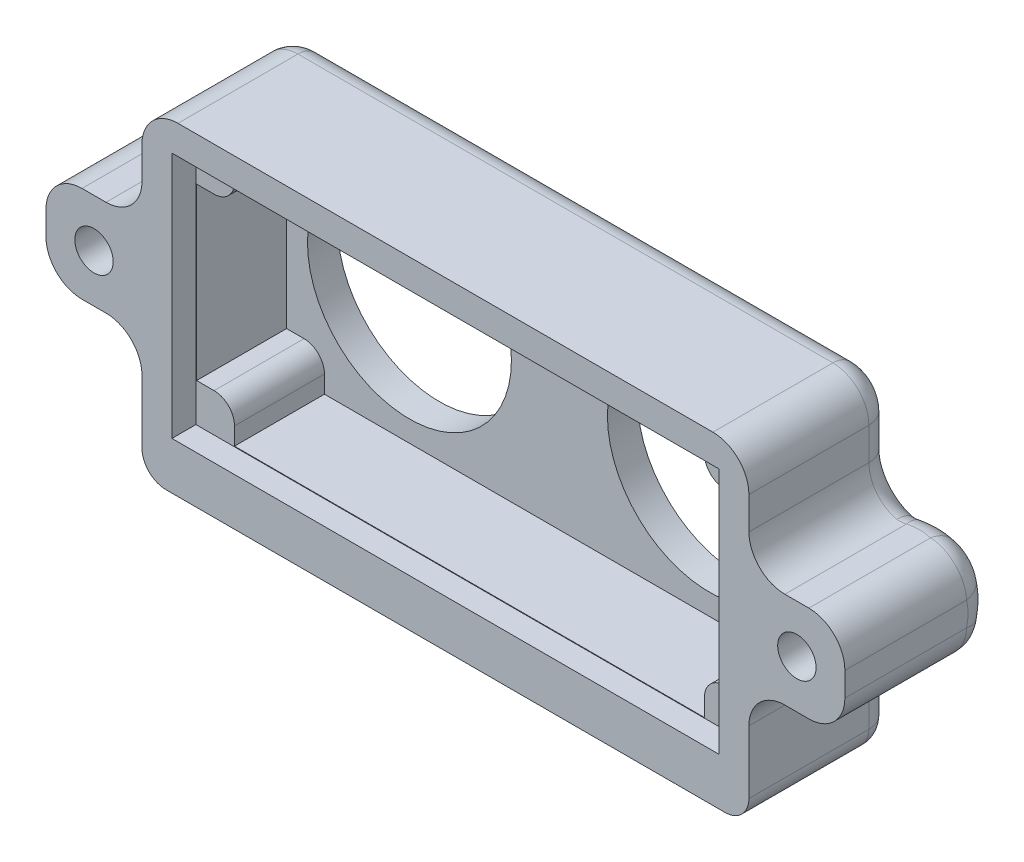
SolidWorks part; units mm, degrees
ref_plane "Plan de face" through (0, 0, 0) normal (0, 0, 1) x (1, 0, 0)
ref_plane "Plan de dessus" through (0, 0, 0) normal (0, 1, 0) x (1, 0, 0)
ref_plane "Plan de droite" through (0, 0, 0) normal (1, 0, 0) x (0, 0, -1)
sketch "Esquisse1" plane through (0, 0, 0) normal (0, 0, 1) x (1, 0, 0)
  line L0 (-21.285, -8.79) -> (21.285, -8.79) construction
  line L1 (-21.285, -8.79) -> (-21.285, 8.79) construction
  line L2 (-21.285, 8.79) -> (21.285, 8.79) construction
  line L3 (21.285, -8.79) -> (21.285, 8.79) construction
  line L4 (-21.285, -8.79) -> (21.285, 8.79) construction
  line L5 (-21.285, 8.79) -> (21.285, -8.79) construction
  line L6 (-22.795, -10.2) -> (22.795, -10.2)
  line L7 (-22.795, -10.2) -> (-22.795, 10.2)
  line L8 (-22.795, 10.2) -> (22.795, 10.2)
  line L9 (22.795, -10.2) -> (22.795, 10.2)
  line L10 (-22.795, -10.2) -> (22.795, 10.2) construction
  line L11 (-22.795, 10.2) -> (22.795, -10.2) construction
  circle A0 centre (-21.285, 8.79) radius 0.825 construction
  circle A1 centre (21.285, 8.79) radius 0.825 construction
  circle A2 centre (21.285, -8.79) radius 0.825 construction
  circle A3 centre (-21.285, -8.79) radius 0.825 construction
  point P0 (0, 0)
  point P5 (0, 0)
  dimension "D5" = 1.65
  dimension "D1" = 42.57
  dimension "D2" = 17.58
  dimension "D3" = 20.4
  dimension "D4" = 45.59
extrude "Boss.-Extru.1" add sketch "Esquisse1" along normal blind 12
sketch "Esquisse3" plane through (0, 0, 12) normal (0, 0, 1) x (1, 0, 0)
  line L0 (22.795, 10.2) -> (-22.795, 10.2) construction
  line L1 (-25.295, 12.7) -> (25.295, 12.7)
  line L2 (-25.295, 12.7) -> (-25.295, -12.7)
  line L3 (-25.295, -12.7) -> (25.295, -12.7)
  line L4 (25.295, 12.7) -> (25.295, -12.7)
  line L5 (-25.295, 12.7) -> (25.295, -12.7) construction
  line L6 (-25.295, -12.7) -> (25.295, 12.7) construction
  line L7 (-22.795, 10.2) -> (-22.795, -10.2) construction
  line L9 (22.795, -10.2) -> (-22.795, -10.2)
  line L10 (22.795, -10.2) -> (22.795, 10.2)
  line L11 (22.795, 10.2) -> (-22.795, 10.2)
  line L12 (-22.795, -10.2) -> (-22.795, 10.2)
  line L13 (22.795, -10.2) -> (-22.795, 10.2) construction
  line L14 (22.795, 10.2) -> (-22.795, -10.2) construction
  point P0 (0, 0)
  point P10 (0, 0)
  dimension "D1" = 2.5
  dimension "D2" = 2.5
extrude "Boss.-Extru.2" add sketch "Esquisse3" against normal blind 12
sketch "Esquisse4" plane through (0, 0, 12) normal (0, 0, 1) x (1, 0, 0)
  line L0 (-19.585, 8.79) -> (-19.585, 10.25)
  line L5 (-23.8, -10.25) -> (23.8, -10.25) construction
  line L6 (-23.8, -10.25) -> (-23.8, 10.25) construction
  line L11 (-23.8, 10.25) -> (23.8, 10.25) construction
  line L12 (23.8, -10.25) -> (23.8, 10.25) construction
  line L13 (-23.8, -10.25) -> (23.8, 10.25) construction
  line L14 (-23.8, 10.25) -> (23.8, -10.25) construction
  line L15 (-23.8, 7.09) -> (-21.285, 7.09)
  line L16 (-21.285, -7.09) -> (-23.8, -7.09)
  line L17 (-19.585, -8.79) -> (-19.585, -10.25)
  line L18 (19.585, -8.79) -> (19.585, -10.25)
  line L19 (21.285, -7.09) -> (23.8, -7.09)
  line L20 (19.585, 8.79) -> (19.585, 10.25)
  line L21 (21.285, 7.09) -> (23.8, 7.09)
  line L22 (-19.585, 10.25) -> (19.585, 10.25)
  line L23 (23.8, 7.09) -> (23.8, -7.09)
  line L24 (-19.585, -10.25) -> (19.585, -10.25)
  line L25 (-23.8, -7.09) -> (-23.8, 7.09)
  arc A4 (-19.585, 8.79) -> (-21.285, 7.09) centre (-21.285, 8.79) cw
  circle A5 centre (-21.285, 8.79) radius 1.7 construction
  circle A6 centre (21.285, 8.79) radius 1.7 construction
  circle A7 centre (21.285, -8.79) radius 1.7 construction
  circle A8 centre (-21.285, -8.79) radius 1.7 construction
  arc A9 (-21.285, -7.09) -> (-19.585, -8.79) centre (-21.285, -8.79) cw
  arc A10 (19.585, -8.79) -> (21.285, -7.09) centre (21.285, -8.79) cw
  arc A11 (21.285, 7.09) -> (19.585, 8.79) centre (21.285, 8.79) cw
  point P5 (0, 0)
  point P10 (0, 0)
  point P22 (0, 0)
  point P27 (0, 0)
  point P32 (0, 0)
  dimension "D1" = 3.4
  dimension "D2" = 20.5
  dimension "D3" = 47.6
extrude "Enlèv. mat.-Extru.1" cut sketch "Esquisse4" against normal blind 12
sketch "Esquisse5" plane through (0, 0, 0) normal (0, 0, -1) x (-1, 0, 0)
  line L1 (-7.5, -14.25) -> (7.5, -14.25)
  line L2 (-7.5, -14.25) -> (-7.5, -10.25)
  line L3 (-7.5, -10.25) -> (7.5, -10.25)
  line L4 (7.5, -14.25) -> (7.5, -10.25)
  line L5 (-7.5, -14.25) -> (7.5, -10.25) construction
  line L6 (-7.5, -10.25) -> (7.5, -14.25) construction
  line L8 (19.585, -10.25) -> (-19.585, -10.25) construction
  point P0 (0, -12.25)
  dimension "D1" = 15
  dimension "D2" = 4
extrude "Boss.-Extru.5" [suppressed] add sketch "Esquisse5" along normal blind 100
sketch "Esquisse7" plane through (0, 12.7, 0) normal (0, 1, 0) x (1, 0, 0)
  line L0 (25.295, 0) -> (-25.295, 0) construction
  line L1 (-5.25, -4) -> (5.25, -4)
  line L2 (-5.25, -4) -> (-5.25, 0)
  line L3 (-5.25, 0) -> (5.25, 0)
  line L4 (5.25, -4) -> (5.25, 0)
  line L5 (-5.25, -4) -> (5.25, 0) construction
  line L6 (-5.25, 0) -> (5.25, -4) construction
  point P0 (0, -2)
  dimension "D1" = 10.5
  dimension "D2" = 4
extrude "Enlèv. mat.-Extru.2" [suppressed] cut sketch "Esquisse7" against normal blind 5
sketch "Esquisse8" plane through (0, -12.7, 0) normal (0, -1, 0) x (1, 0, 0)
  line L0 (-25.295, 12) -> (25.295, 12) construction
  line L1 (-6.1299, 6) -> (6.1299, 6)
  line L2 (-6.1299, 6) -> (-6.1299, 12)
  line L3 (-6.1299, 12) -> (6.1299, 12)
  line L4 (6.1299, 6) -> (6.1299, 12)
  line L5 (-6.1299, 6) -> (6.1299, 12) construction
  line L6 (-6.1299, 12) -> (6.1299, 6) construction
  point P0 (0, 9)
  dimension "D1" = 6
extrude "Boss.-Extru.6" [suppressed] add sketch "Esquisse8" along normal blind 7
sketch "Esquisse9" [suppressed] plane through (0, 0, 0) normal (0, 0, -1) x (-1, 0, 0)
  line L0 (-6.1299, -19.7) -> (-6.1299, -12.7) construction
  circle A0 centre (0, -16.2) radius 1.6
  point P5 (-6.1299, -16.2)
  dimension "D1" = 3.2
extrude "Enlèv. mat.-Extru.3" [suppressed] cut sketch "Esquisse9" against normal blind 6
sketch "Esquisse10" [suppressed] plane through (0, 0, 0) normal (0, 0, -1) x (-1, 0, 0)
  line L0 (6.1299, -19.7) -> (-6.1299, -19.7) construction
  line L1 (3.2332, -16.2) -> (1.6166, -13.4)
  line L2 (1.6166, -13.4) -> (-1.6166, -13.4)
  line L3 (-1.6166, -13.4) -> (-3.2332, -16.2)
  line L4 (-3.2332, -16.2) -> (-1.6166, -19)
  line L5 (-1.6166, -19) -> (1.6166, -19)
  line L6 (1.6166, -19) -> (3.2332, -16.2)
  circle A0 centre (0, -16.2) radius 2.8 construction
  dimension "D1" = 5.6
extrude "Enlèv. mat.-Extru.4" [suppressed] cut sketch "Esquisse10" against normal blind 2.5
fillet "Congé1" [suppressed] radius 3
fillet "Congé2" radius 3 2 edges at (25.295, 12.7, 6) (-25.295, 12.7, 6)
sketch "Esquisse11" [suppressed] plane through (0, 0, -100) normal (0, 0, -1) x (-1, 0, 0)
  line L1 (-15, -14.25) -> (15, -14.25)
  line L2 (-15, -14.25) -> (-15, 19.75)
  line L3 (-15, 19.75) -> (15, 19.75)
  line L4 (15, -14.25) -> (15, 19.75)
  line L5 (7.5, -10.25) -> (-7.5, -10.25) construction
  line L6 (-10, 14.75) -> (10, 14.75) construction
  line L7 (-10, 14.75) -> (-10, -5.25) construction
  line L8 (-10, -5.25) -> (10, -5.25) construction
  line L9 (10, 14.75) -> (10, -5.25) construction
  line L10 (-7.5, -14.25) -> (7.5, -14.25) construction
  circle A0 centre (-10, 14.75) radius 1.1581
  circle A1 centre (10, 14.75) radius 1.184
  circle A2 centre (10, -5.25) radius 1.2948
  circle A3 centre (-10, -5.25) radius 1.2189
  point P6 (0, 19.75)
  point P12 (0, -5.25)
  dimension "D1" = 5
  dimension "D2" = 20
  dimension "D3" = 20
  dimension "D4" = 5
  dimension "D5" = 5
extrude "Boss.-Extru.7" [suppressed] add sketch "Esquisse11" against normal blind 7.5
fillet "Congé3" [suppressed] radius 3
sketch "Esquisse12" [suppressed] plane through (0, 0, -92.5) normal (0, 0, 1) x (1, 0, 0)
  line L0 (-10, 14.75) -> (10, -5.25) construction
  line L1 (-12.2862, 17.0362) -> (-13.123, 13.9132)
  line L2 (-13.123, 13.9132) -> (-10.8368, 11.627)
  line L3 (-10.8368, 11.627) -> (-7.7138, 12.4638)
  line L4 (-7.7138, 12.4638) -> (-6.877, 15.5868)
  line L5 (-6.877, 15.5868) -> (-9.1632, 17.873)
  line L6 (-9.1632, 17.873) -> (-12.2862, 17.0362)
  line L7 (12.2862, 17.0362) -> (9.1632, 17.873)
  line L8 (9.1632, 17.873) -> (6.877, 15.5868)
  line L9 (6.877, 15.5868) -> (7.7138, 12.4638)
  line L10 (7.7138, 12.4638) -> (10.8368, 11.627)
  line L11 (10.8368, 11.627) -> (13.123, 13.9132)
  line L12 (13.123, 13.9132) -> (12.2862, 17.0362)
  line L13 (12.2862, -7.5362) -> (13.123, -4.4132)
  line L14 (13.123, -4.4132) -> (10.8368, -2.127)
  line L15 (10.8368, -2.127) -> (7.7138, -2.9638)
  line L16 (7.7138, -2.9638) -> (6.877, -6.0868)
  line L17 (6.877, -6.0868) -> (9.1632, -8.373)
  line L18 (9.1632, -8.373) -> (12.2862, -7.5362)
  line L19 (-7.7138, -2.9638) -> (-10.8368, -2.127)
  line L20 (-10.8368, -2.127) -> (-13.123, -4.4132)
  line L21 (-13.123, -4.4132) -> (-12.2862, -7.5362)
  line L22 (-12.2862, -7.5362) -> (-9.1632, -8.373)
  line L23 (-9.1632, -8.373) -> (-6.877, -6.0868)
  line L24 (-6.877, -6.0868) -> (-7.7138, -2.9638)
  line L26 (10, 14.75) -> (-10, -5.25) construction
  circle A0 centre (-10, 14.75) radius 2.8 construction
  circle A1 centre (10, 14.75) radius 2.8 construction
  circle A2 centre (10, -5.25) radius 2.8 construction
  circle A3 centre (-10, -5.25) radius 2.8 construction
  dimension "D1" = 5.6
extrude "Enlèv. mat.-Extru.5" [suppressed] cut sketch "Esquisse12" against normal blind 2.5
sketch "Esquisse13" [suppressed] plane through (7.5, 0, 0) normal (1, 0, 0) x (0, 0, -1)
  line L0 (-6, -10.25) -> (92.5, 9.75)
  line L1 (92.5, 9.75) -> (92.5, -10.25)
  line L3 (92.5, -10.25) -> (-6, -10.25)
  line L11 (92.5, -10.25) -> (0, -10.25) construction
  dimension "D1" = 20
extrude "Boss.-Extru.8" [suppressed] add sketch "Esquisse13" against normal blind 5 from offset 5 offset against normal yes
fillet "Congé4" [suppressed] radius 3
fillet "Congé5" [suppressed] radius 3
sketch "Esquisse14" plane through (-25.295, 0, 0) normal (-1, 0, 0) x (0, 0, 1)
  line L0 (0, 9.7) -> (0, -12.7) construction
  line L1 (0, 4) -> (12, 4)
  line L2 (0, 4) -> (0, -4)
  line L3 (0, -4) -> (12, -4)
  line L4 (12, 4) -> (12, -4)
  line L5 (12, 9.7) -> (12, -12.7) construction
  dimension "D1" = 8
extrude "Boss.-Extru.9" add sketch "Esquisse14" along normal blind 8
sketch "Esquisse15" plane through (25.295, 0, 0) normal (1, 0, 0) x (0, 0, -1)
  line L0 (0, -12.7) -> (0, 9.7) construction
  line L5 (0, -12.7) -> (0, 9.7) construction
  line L6 (0, 4) -> (-12, 4)
  line L7 (0, 4) -> (0, -4)
  line L8 (0, -4) -> (-12, -4)
  line L9 (-12, 4) -> (-12, -4)
  line L10 (-12, -12.7) -> (-12, 9.7) construction
  line L11 (-12, 9.7) -> (-12, -9.7) construction
  point P4 (-12, 0)
  dimension "D1" = 8
extrude "Boss.-Extru.10" add sketch "Esquisse15" along normal blind 8
sketch "Esquisse16" plane through (0, 0, 12) normal (0, 0, 1) x (1, 0, 0)
  line L0 (-33.295, 4) -> (-25.295, 4) construction
  line L1 (-33.295, -4) -> (-33.295, 4) construction
  line L2 (33.295, 4) -> (25.295, 4) construction
  circle A0 centre (-29.295, 0) radius 1.6
  circle A1 centre (29.295, 0) radius 1.6
  point P7 (-29.295, 4)
  point P10 (-33.295, 0)
  point P13 (29.295, 4)
  dimension "D1" = 3.2
  dimension "D2" = 3.2
extrude "Enlèv. mat.-Extru.6" cut sketch "Esquisse16" against normal blind 6
sketch "Esquisse17" plane through (0, 0, 0) normal (0, 0, 1) x (1, 0, 0)
  line L1 (-26.0618, 0) -> (-27.6784, 2.8) construction
  line L2 (-27.6784, 2.8) -> (-30.9116, 2.8) construction
  line L3 (-30.9116, 2.8) -> (-32.5282, 0) construction
  line L4 (-32.5282, 0) -> (-30.9116, -2.8) construction
  line L5 (-30.9116, -2.8) -> (-27.6784, -2.8) construction
  line L6 (-27.6784, -2.8) -> (-26.0618, 0) construction
  line L7 (32.7591, 0) -> (31.0271, 3) construction
  line L8 (31.0271, 3) -> (27.5629, 3) construction
  line L9 (27.5629, 3) -> (25.8309, 0) construction
  line L10 (25.8309, 0) -> (27.5629, -3) construction
  line L11 (27.5629, -3) -> (31.0271, -3) construction
  line L12 (31.0271, -3) -> (32.7591, 0) construction
  circle A0 centre (-29.295, 0) radius 2.8
  circle A1 centre (29.295, 0) radius 3
  dimension "D1" = 5.6
  dimension "D2" = 6
extrude "Enlèv. mat.-Extru.7" cut sketch "Esquisse17" along normal blind 9.5
fillet "Congé6" radius 3 8 edges at (-25.295, -4, 6) (-33.295, -4, 6) (-33.295, 4, 6) (-25.295, 4, 6) (25.295, 4, 6) (33.295, 4, 6) (33.295, -4, 6) (25.295, -4, 6)
sketch "Esquisse18" plane through (0, -12.7, 0) normal (0, -1, 0) x (1, 0, 0)
  line L0 (-25.295, 0) -> (25.295, 0) construction
  line L1 (-25.295, 12) -> (25.295, 12)
  line L2 (-25.295, 12) -> (-25.295, 0)
  line L3 (-25.295, 0) -> (25.295, 0)
  line L4 (25.295, 12) -> (25.295, 0)
extrude "Boss.-Extru.11" add sketch "Esquisse18" along normal blind 1.55
fillet "Congé7" [suppressed] radius 3
sketch "Esquisse19" plane through (-23.8, 0, 0) normal (1, 0, 0) x (0, 0, -1)
  line L1 (-12, 7.09) -> (0, 7.09)
  line L2 (-12, 7.09) -> (-12, -7.09)
  line L3 (-12, -7.09) -> (0, -7.09)
  line L4 (0, 7.09) -> (0, -7.09)
extrude "Boss.-Extru.12" add sketch "Esquisse19" along normal blind 1.06 contours L2 L1 L4 L3
sketch "Esquisse20" plane through (23.8, 0, 0) normal (-1, 0, 0) x (0, 0, 1)
  line L1 (12, 7.09) -> (0, 7.09)
  line L2 (12, 7.09) -> (12, -7.09)
  line L3 (12, -7.09) -> (0, -7.09)
  line L4 (0, 7.09) -> (0, -7.09)
extrude "Boss.-Extru.13" add sketch "Esquisse20" along normal blind 1.06
fillet "Congé8" [suppressed] radius 2.5
fillet "Congé9" [suppressed] radius 3
sketch "Esquisse21" plane through (0, 0, 0) normal (0, 0, -1) x (-1, 0, 0)
  line L0 (-12.5, 0) -> (12.5, 0) construction
  line L5 (-21.285, 8.79) -> (21.285, 8.79) construction
  line L6 (-21.285, 8.79) -> (-21.285, -8.79) construction
  line L7 (-21.285, -8.79) -> (21.285, -8.79) construction
  line L8 (21.285, 8.79) -> (21.285, -8.79) construction
  line L13 (-19.585, 10.25) -> (19.585, 10.25) construction
  line L14 (-22.74, -10.25) -> (22.74, -10.25)
  line L25 (-22.74, -10.25) -> (-22.74, 10.25)
  line L26 (-22.74, 10.25) -> (22.74, 10.25)
  line L27 (22.74, -10.25) -> (22.74, 10.25)
  line L28 (-22.74, -10.25) -> (22.74, 10.25) construction
  line L29 (-22.74, 10.25) -> (22.74, -10.25) construction
  line L30 (-22.74, 7.09) -> (-22.74, -7.09) construction
  circle A0 centre (-12.5, 0) radius 8.5
  circle A1 centre (12.5, 0) radius 8.5
  point P0 (0, 0)
  point P12 (0, 0)
  point P23 (0, 0)
  dimension "D3" = 17
  dimension "D4" = 25
extrude "Boss.-Extru.14" add sketch "Esquisse21" against normal blind 2.5
fillet "Congé10" radius 2 11 edges at (25.295, -10.625, 0) (26.1737, -4.8787, 0) (26.1737, 4.8787, 0) (25.295, 8.35, 0) (24.4163, 11.8213, 0) (-25.295, -10.625, 0) (-26.1737, -4.8787, 0) (-26.1737, 4.8787, 0) (-25.295, 8.35, 0) (-24.4163, 11.8213, 0) (0, 12.7, 0)
fillet "Congé11" radius 2 5 edges at (-25.295, -14.25, 7) (-24.7092, -14.25, 0.5858) (25.295, -14.25, 7) (24.7092, -14.25, 0.5858) (0, -14.25, 0)
sketch "Esquisse22" plane through (0, 0, 12) normal (0, 0, 1) x (1, 0, 0)
  line L1 (-22.8, -10.3) -> (22.8, -10.3)
  line L2 (-22.8, -10.3) -> (-22.8, 10.3)
  line L3 (-22.8, 10.3) -> (22.8, 10.3)
  line L4 (22.8, -10.3) -> (22.8, 10.3)
  line L5 (-22.8, -10.3) -> (22.8, 10.3) construction
  line L6 (-22.8, 10.3) -> (22.8, -10.3) construction
  point P0 (0, 0)
  dimension "D1" = 45.6
  dimension "D2" = 20.6
extrude "Enlèv. mat.-Extru.8" cut sketch "Esquisse22" against normal blind 2
